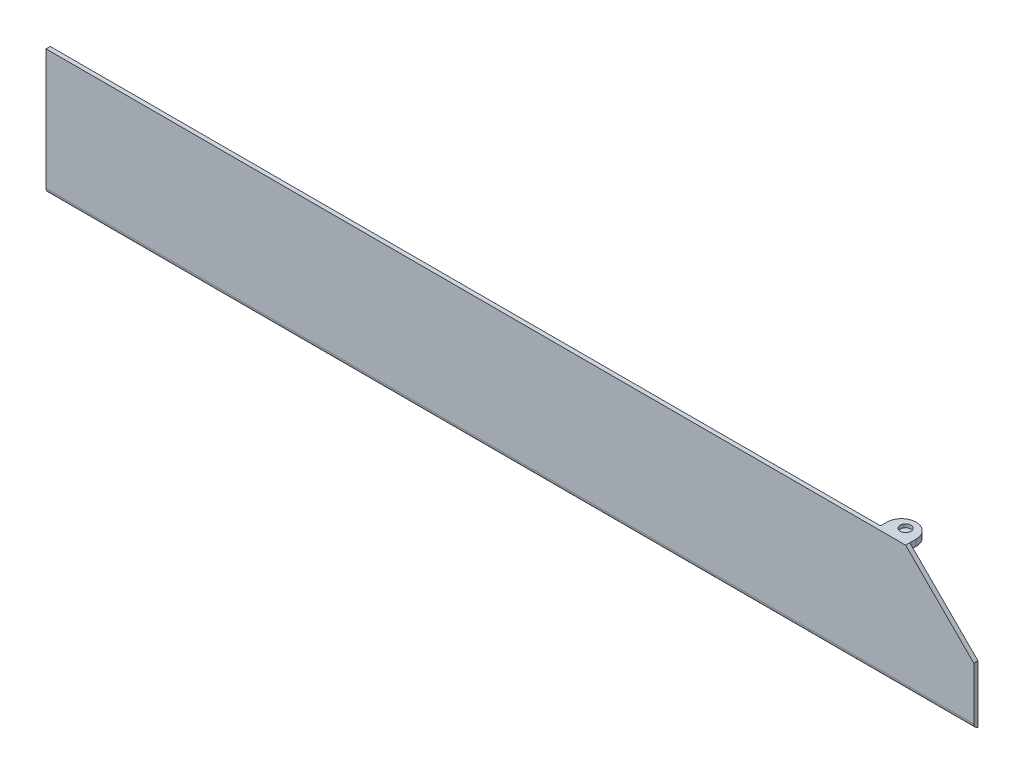
SolidWorks part; units mm, degrees
ref_plane "Front Plane" through (0, 0, 0) normal (0, 0, 1) x (1, 0, 0)
ref_plane "Top Plane" through (0, 0, 0) normal (0, 1, 0) x (1, 0, 0)
ref_plane "Right Plane" through (0, 0, 0) normal (1, 0, 0) x (0, 0, -1)
sketch "Sketch1" plane through (0, 0, 0) normal (0, 0, 1) x (1, 0, 0)
  line L0 (0, 0) -> (885, 0)
  line L1 (885, 0) -> (885, 55)
  line L2 (885, 55) -> (820, 120)
  line L3 (820, 120) -> (0, 120)
  line L4 (0, 120) -> (0, 0)
  dimension "D1" = 120
  dimension "D2" = 885
  dimension "D3" = 55
  dimension "D4" = 135
extrude "Boss-Extrude1" add sketch "Sketch1" along normal blind 4
sketch "Sketch2" plane through (0, 0, 0) normal (0, 0, -1) x (-1, 0, 0)
  line L0 (0, 120) -> (0, 0) construction
  line L1 (-25, 85) -> (-20, 85)
  line L2 (-25, 85) -> (-25, 95)
  line L3 (-25, 95) -> (-20, 95)
  line L4 (-20, 85) -> (-20, 95)
  line L5 (-20, 30) -> (-25, 30)
  line L6 (-20, 30) -> (-20, 40)
  line L7 (-20, 40) -> (-25, 40)
  line L8 (-25, 30) -> (-25, 40)
  line L9 (-820, 120) -> (0, 120) construction
  point P10 (-20, 90)
  point P13 (-20, 35)
  dimension "D1" = 5
  dimension "D2" = 5
  dimension "D3" = 10
  dimension "D4" = 10
  dimension "D5" = 20
  dimension "D6" = 20
  dimension "D7" = 30
  dimension "D8" = 85
extrude "Boss-Extrude2" add sketch "Sketch2" along normal blind 20
sketch "Sketch3" plane through (25, 0, 0) normal (1, 0, 0) x (0, 0, -1)
  line L0 (20, 95) -> (20, 85) construction
  line L1 (20, 95) -> (0, 95) construction
  line L2 (20, 40) -> (20, 30) construction
  line L3 (20, 40) -> (0, 40) construction
  circle A0 centre (10, 90) radius 2.65
  circle A1 centre (10, 35) radius 2.65
  dimension "D1" = 5.3
  dimension "D2" = 10
  dimension "D3" = 5
  dimension "D6" = 5.3
  dimension "D4" = 10
  dimension "D5" = 5
extrude "Cut-Extrude1" cut sketch "Sketch3" against normal blind 20
fillet "Fillet1" radius 5 4 edges at (22.5, 30, -20) (22.5, 40, -20) (22.5, 85, -20) (22.5, 95, -20)
sketch "Sketch4" plane through (0, 0, 0) normal (0, 0, -1) x (-1, 0, 0)
  line L0 (-885, 0) -> (-885, 55) construction
  line L1 (-865, 35) -> (-860, 35)
  line L2 (-865, 35) -> (-865, 25)
  line L3 (-865, 25) -> (-860, 25)
  line L4 (-860, 35) -> (-860, 25)
  dimension "D1" = 10
  dimension "D2" = 5
  dimension "D3" = 20
  dimension "D4" = 20
extrude "Boss-Extrude3" add sketch "Sketch4" along normal blind 20
sketch "Sketch5" plane through (865, 0, 0) normal (1, 0, 0) x (0, 0, -1)
  line L0 (0, 35) -> (0, 25) construction
  line L1 (20, 35) -> (0, 35) construction
  circle A0 centre (10, 30) radius 2.65
  dimension "D3" = 5.3
  dimension "D1" = 10
  dimension "D2" = 5
extrude "Cut-Extrude2" cut sketch "Sketch5" against normal blind 20
fillet "Fillet2" radius 5 2 edges at (862.5, 25, -20) (862.5, 35, -20)
sketch "Sketch6" plane through (0, 0, 0) normal (0, 0, -1) x (-1, 0, 0)
  line L1 (-820, 120) -> (-792, 120)
  line L2 (-820, 120) -> (-820, 114)
  line L3 (-820, 114) -> (-792, 114)
  line L4 (-792, 120) -> (-792, 114)
  dimension "D1" = 6
  dimension "D2" = 28
extrude "Boss-Extrude4" add sketch "Sketch6" along normal blind 20
sketch "Sketch7" plane through (0, 120, 0) normal (0, 1, 0) x (1, 0, 0)
  line L0 (792, 20) -> (792, 0) construction
  line L1 (792, 20) -> (820, 20) construction
  circle A0 centre (806, 10) radius 5.1
  dimension "D1" = 10.2
  dimension "D2" = 14
  dimension "D3" = 10
extrude "Cut-Extrude3" cut sketch "Sketch7" against normal blind 3.2
fillet "Fillet3" radius 14 2 edges at (792, 117, -20) (820, 117, -20)
fillet "Fillet4" radius 5 1 edges at (442.5, 0, 4)
